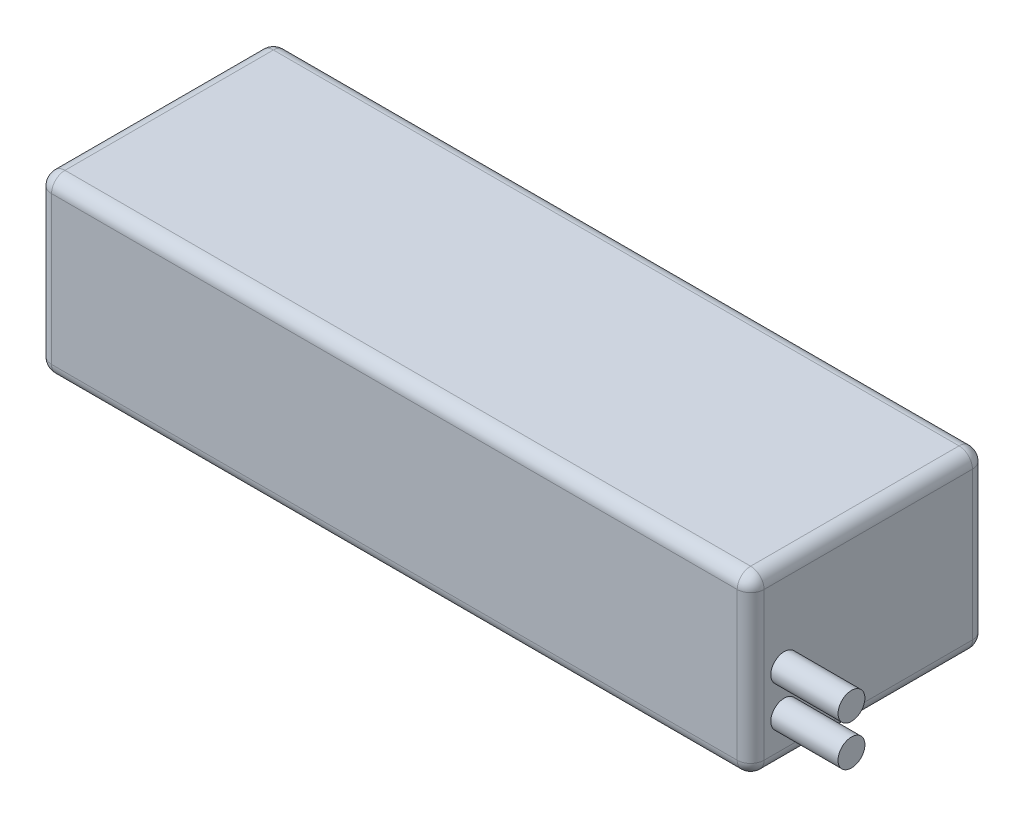
SolidWorks part; units mm, degrees
ref_plane "Front Plane" through (0, 0, 0) normal (0, 0, 1) x (1, 0, 0)
ref_plane "Top Plane" through (0, 0, 0) normal (0, 1, 0) x (1, 0, 0)
ref_plane "Right Plane" through (0, 0, 0) normal (1, 0, 0) x (0, 0, -1)
sketch "Sketch1" plane through (0, 0, 0) normal (0, 1, 0) x (1, 0, 0)
  line L1 (-53, 17.5) -> (53, 17.5)
  line L2 (-53, 17.5) -> (-53, -17.5)
  line L3 (-53, -17.5) -> (53, -17.5)
  line L4 (53, 17.5) -> (53, -17.5)
  line L5 (-53, 17.5) -> (53, -17.5) construction
  line L6 (-53, -17.5) -> (53, 17.5) construction
  point P0 (0, 0)
  dimension "D1" = 106
  dimension "D2" = 35
extrude "Boss-Extrude1" add sketch "Sketch1" along normal blind 26
fillet "Fillet1" radius 2 12 edges at (0, 0, 17.5) (0, 0, -17.5) (0, 26, -17.5) (0, 26, 17.5) (-53, 13, 17.5) (53, 13, 17.5) (-53, 0, 0) (-53, 26, 0) (-53, 13, -17.5) (53, 13, -17.5) (53, 0, 0) (53, 26, 0)
sketch "Sketch2" plane through (53, 0, 0) normal (1, 0, 0) x (0, 0, -1)
  line L2 (-12.5, 24) -> (-12.5, 2) construction
  line L3 (15.5, 24) -> (-15.5, 24) construction
  line L4 (-15.5, 2) -> (15.5, 2) construction
  line L5 (-15.5, 24) -> (-15.5, 2) construction
  circle A0 centre (-12.5, 6.5) radius 2
  circle A1 centre (-12.5, 12.5) radius 2
  point P10 (-12.4851, 2)
  point P13 (-12.5, 10.4269)
  point P14 (-12.5, 10.4631)
  dimension "D1" = 4
  dimension "D2" = 4
  dimension "D3" = 3
  dimension "D4" = 6
  dimension "D5" = 4.5
extrude "Boss-Extrude2" add sketch "Sketch2" along normal blind 10
